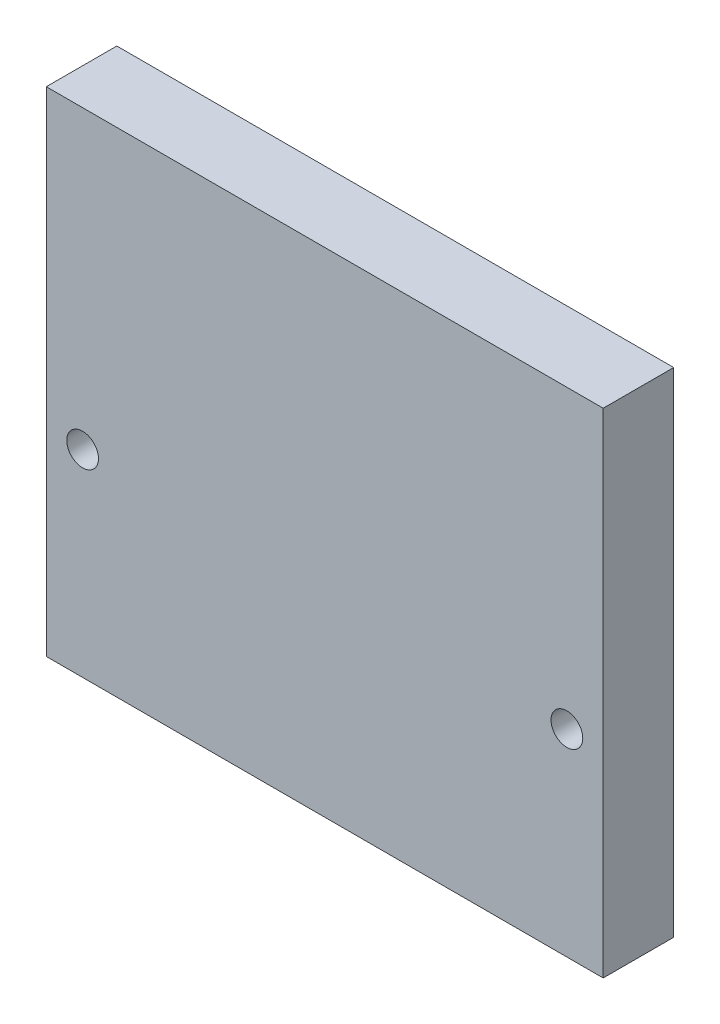
SolidWorks part; units mm, degrees
ref_plane "Top" through (0, 0, 0) normal (0, 0, 1) x (1, 0, 0)
ref_plane "Front" through (0, 0, 0) normal (0, 1, 0) x (1, 0, 0)
ref_plane "Right" through (0, 0, 0) normal (1, 0, 0) x (0, 0, -1)
sketch "Sketch1" plane through (0, 0, 0) normal (0, 0, 1) x (1, 0, 0)
  line L1 (0, 0) -> (79, 0)
  line L2 (0, 0) -> (0, 70)
  line L3 (0, 70) -> (79, 70)
  line L4 (79, 0) -> (79, 70)
  dimension "D1" = 79
  dimension "D2" = 70
extrude "Boss-Extrude1" add sketch "Sketch1" along normal blind 10
sketch "Sketch4" plane through (0, 0, 10) normal (0, 0, 1) x (1, 0, 0)
  line L0 (5.15, 28) -> (73.85, 28)
  line L2 (79, 0) -> (79, 70) construction
  line L5 (79, 70) -> (0, 70) construction
  point P2 (39.5, 28)
  dimension "D1" = 68.7
  dimension "D2" = 39.5
  dimension "D3" = 42
hole_wizard "M4 Clearance Hole1" positions "Sketch5" profile "Sketch6" hole size "M4" standard "DIN" end condition through all
sketch "Sketch5" plane through (0, 0, 10) normal (0, 0, 1) x (1, 0, 0)
  point P0 (5.15, 28)
  point P3 (73.85, 28)
sketch "Sketch6" plane through (5.15, 28, 10) normal (1, 0, 0) x (0, -1, 0)
  line L0 (0, 0) -> (0, 10)
  line L1 (0, 10) -> (2.25, 10)
  line L2 (2.25, 10) -> (2.25, 0)
  line L5 (2.25, 0) -> (0, 0)
  line L11 (0, -6.35) -> (0, 107.95) construction
  dimension "Thru Hole Dia." = 4.5
  dimension "Thru Hole Depth" = 10
sketch "Sketch11" plane through (0, 0, 0) normal (0, 0, -1) x (-1, 0, 0)
  line L0 (-79, 70) -> (0, 70) construction
  line L1 (-69.6353, 28) -> (-71.7427, 31.65)
  line L2 (-71.7427, 31.65) -> (-75.9573, 31.65)
  line L3 (-75.9573, 31.65) -> (-78.0647, 28)
  line L4 (-78.0647, 28) -> (-75.9573, 24.35)
  line L5 (-75.9573, 24.35) -> (-71.7427, 24.35)
  line L6 (-71.7427, 24.35) -> (-69.6353, 28)
  line L7 (-9.3647, 28) -> (-7.2573, 24.35)
  line L8 (-7.2573, 24.35) -> (-3.0427, 24.35)
  line L9 (-3.0427, 24.35) -> (-0.9353, 28)
  line L10 (-0.9353, 28) -> (-3.0427, 31.65)
  line L11 (-3.0427, 31.65) -> (-7.2573, 31.65)
  line L12 (-7.2573, 31.65) -> (-9.3647, 28)
  circle A0 centre (-73.85, 28) radius 3.65 construction
  circle A1 centre (-5.15, 28) radius 3.65 construction
  dimension "D1" = 7.3
  dimension "D2" = 7.3
extrude "Cut-Extrude3" cut sketch "Sketch11" against normal blind 3.5
